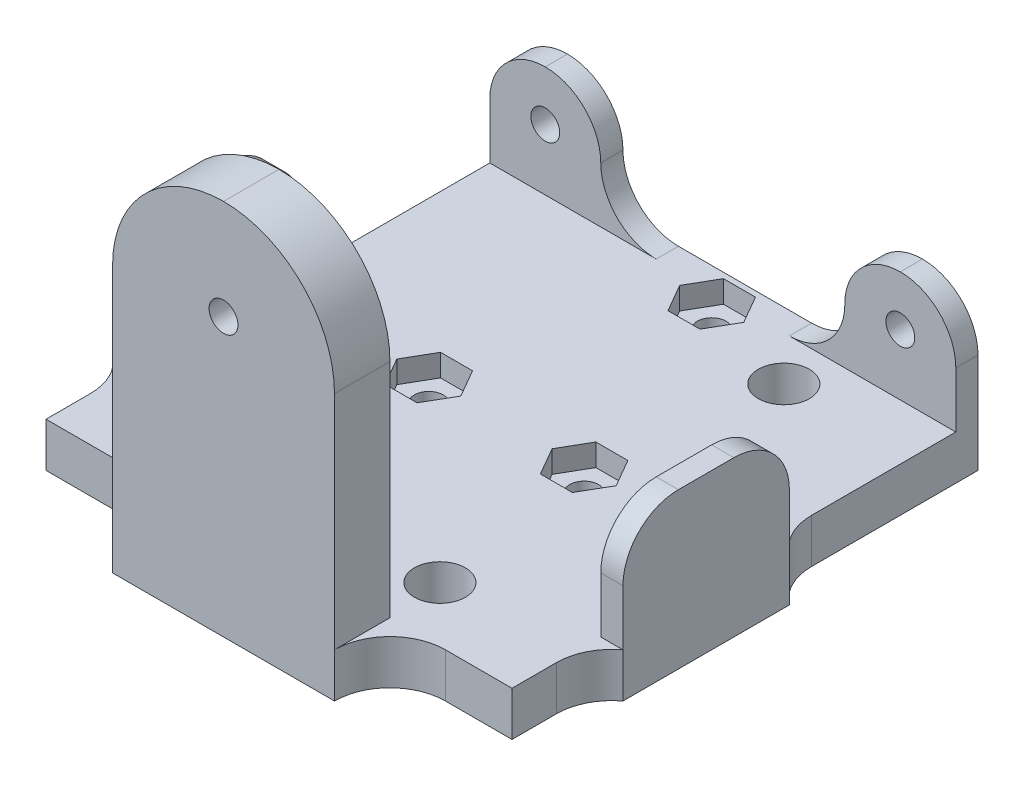
SolidWorks part; units mm, degrees
ref_plane "前视基准面" through (0, 0, 0) normal (0, 0, 1) x (1, 0, 0)
ref_plane "上视基准面" through (0, 0, 0) normal (0, 1, 0) x (1, 0, 0)
ref_plane "右视基准面" through (0, 0, 0) normal (1, 0, 0) x (0, 0, -1)
sketch "草图1" plane through (0, 0, 0) normal (0, 1, 0) x (1, 0, 0)
  line L0 (-23, -10.5) -> (23, -10.5) construction
  line L1 (-23, -23.5) -> (23, -23.5) construction
  line L2 (-23, -23.5) -> (-23, 23.5) construction
  line L3 (-23, 23.5) -> (23, 23.5) construction
  line L4 (23, -23.5) -> (23, 23.5) construction
  line L5 (-23, -23.5) -> (23, 23.5) construction
  line L6 (-23, 23.5) -> (23, -23.5) construction
  line L7 (-23, 4.5) -> (23, 4.5) construction
  line L8 (-21, 23.5) -> (-21, -18.5) construction
  line L9 (21, 23.5) -> (21, -23.5) construction
  line L10 (-23, -18.5) -> (23, -18.5) construction
  line L11 (-10, -23.5) -> (10, -23.5) construction
  line L12 (-23, 21.5) -> (23, 21.5) construction
  line L13 (-11, 23.5) -> (-11, -18.5) construction
  line L14 (11, 23.5) -> (11, -18.5) construction
  line L15 (-21, 23.5) -> (-21, 4.5)
  line L16 (-23, 4.5) -> (-21, 4.5)
  line L17 (-23, -10.5) -> (-21, -10.5)
  line L18 (-21, -10.5) -> (-21, -18.5)
  line L19 (-21, -18.5) -> (-11, -18.5)
  line L20 (-21, -21.4565) -> (-21, -22.1289) construction
  line L21 (-10, -23.5) -> (10, -23.5)
  line L22 (11, -18.5) -> (21, -18.5)
  line L23 (21, -18.5) -> (21, -10.5)
  line L24 (21, -10.5) -> (23, -10.5)
  line L25 (23, 4.5) -> (21, 4.5)
  line L26 (21, 4.5) -> (21, 23.5)
  line L27 (-10, -23.5) -> (-10, -18.5)
  line L28 (-10, -18.5) -> (-11, -18.5)
  line L29 (10, -23.5) -> (10, -18.5)
  line L30 (10, -18.5) -> (11, -18.5)
  line L31 (-23, 4.5) -> (-23, -10.5)
  line L32 (23, 4.5) -> (23, -10.5)
  line L33 (21, 23.5) -> (-21, 23.5)
  point P0 (0, 0)
  point P19 (0, -23.5)
  point P25 (-21, 4.5)
  point P26 (-21, -10.5)
  point P27 (-21, -18.5)
  point P28 (-11, -18.5)
  point P29 (11, -18.5)
  point P30 (21, -18.5)
  point P31 (21, -10.5)
  point P32 (21, 4.5)
  dimension "D1" = 46
  dimension "D2" = 47
  dimension "D3" = 13
  dimension "D4" = 15
  dimension "D5" = 2
  dimension "D6" = 2
  dimension "D7" = 5
  dimension "D8" = 10
  dimension "D9" = 2
  dimension "D10" = 10
  dimension "D11" = 10
extrude "凸台-拉伸1" add sketch "草图1" along normal blind 4
sketch "草图2" plane through (0, 4, 0) normal (0, 1, 0) x (1, 0, 0)
  line L1 (-23, 4.5) -> (-21, 4.5)
  line L2 (-23, 4.5) -> (-23, -10.5)
  line L3 (-23, -10.5) -> (-21, -10.5)
  line L4 (-21, 4.5) -> (-21, -10.5)
  line L5 (21, 4.5) -> (23, 4.5)
  line L6 (21, 4.5) -> (21, -10.5)
  line L7 (21, -10.5) -> (23, -10.5)
  line L8 (23, 4.5) -> (23, -10.5)
  line L9 (-21, 23.5) -> (-11, 23.5)
  line L10 (-21, 23.5) -> (-21, 21.5)
  line L11 (-21, 21.5) -> (-11, 21.5)
  line L12 (-11, 23.5) -> (-11, 21.5)
  line L13 (21, 23.5) -> (11, 23.5)
  line L14 (21, 23.5) -> (21, 21.5)
  line L15 (21, 21.5) -> (11, 21.5)
  line L16 (11, 23.5) -> (11, 21.5)
  line L17 (-10, -18.5) -> (10, -18.5)
  line L18 (-10, -18.5) -> (-10, -23.5)
  line L19 (-10, -23.5) -> (10, -23.5)
  line L20 (10, -18.5) -> (10, -23.5)
  line M5 (-23, 4.5) -> (-23, -10.5)
  line M6 (-23, -10.5) -> (-21, -10.5)
  line M14 (21, -10.5) -> (23, -10.5)
  line M15 (23, -10.5) -> (23, 4.5)
  line M16 (23, 4.5) -> (21, 4.5)
  line M17 (21, 4.5) -> (21, 23.5)
  line M18 (21, 23.5) -> (-21, 23.5)
  line M19 (-21, 23.5) -> (-21, 4.5)
  line M20 (-21, 4.5) -> (-23, 4.5)
  dimension "D1" = 10
  dimension "D2" = 2
  dimension "D3" = 10
  dimension "D4" = 2
extrude "凸台-拉伸2" add sketch "草图2" along normal blind 10 contours L4 M20 M5 M6 | L12 L11 M18 M19 | L16 L15 M18 M17 | L6 M16 M14 M15 region at (22, 4, 3) region at (16, 4, -22.5) region at (-16, 4, -22.5) region at (-22, 4, 3)
sketch "草图3" plane through (0, 4, 0) normal (0, 1, 0) x (1, 0, 0)
  line L1 (-10, -18.5) -> (10, -18.5)
  line L2 (-10, -18.5) -> (-10, -23.5)
  line L3 (-10, -23.5) -> (10, -23.5)
  line L4 (10, -18.5) -> (10, -23.5)
extrude "凸台-拉伸3" add sketch "草图3" along normal blind 30
sketch "草图4" plane through (0, 0, -23.5) normal (0, 0, -1) x (-1, 0, 0)
  line L0 (-11, 9.5) -> (-21, 9.5) construction
  line L1 (-11, 14) -> (-11, 4) construction
  line L2 (-21, 14) -> (-21, 0) construction
  line L3 (11, 9.5) -> (21, 9.5) construction
  line L4 (11, 14) -> (11, 4) construction
  line L6 (21, 14) -> (21, 0) construction
  line L7 (-16, 14) -> (-16, 0) construction
  line L8 (-21, 14) -> (-11, 14) construction
  line L9 (-21, 0) -> (21, 0) construction
  line L10 (16, 14) -> (16, 0) construction
  line L11 (11, 14) -> (21, 14) construction
  circle A0 centre (-16, 9.5) radius 1.3
  circle A1 centre (16, 9.5) radius 1.3
  point P23 (-16, 9.5)
  point P24 (16, 9.5)
  dimension "D1" = 9.5
extrude "切除-拉伸1" cut sketch "草图4" against normal blind 2
sketch "草图5" plane through (0, 0, 18.5) normal (0, 0, -1) x (-1, 0, 0)
  line L0 (-10, 25) -> (10, 25) construction
  line L1 (-10, 34) -> (-10, 4) construction
  line L2 (10, 34) -> (10, 4) construction
  line L3 (0, 34) -> (0, 4) construction
  line L4 (-10, 34) -> (10, 34) construction
  line L5 (-11, 4) -> (11, 4) construction
  circle A0 centre (0, 25) radius 1.3
  point P12 (0, 25)
  dimension "D1" = 21
extrude "切除-拉伸2" cut sketch "草图5" against normal through all
sketch "草图6" plane through (0, 0, 18.5) normal (0, 0, -1) x (-1, 0, 0)
  line L0 (0, 34) -> (0, 4) construction
  line L1 (-10, 34) -> (10, 34) construction
  line L2 (-11, 4) -> (11, 4) construction
  line L3 (10, 25) -> (-10, 25) construction
  line L4 (10, 34) -> (10, 4) construction
  line L5 (-10, 34) -> (-10, 4) construction
  line L7 (2.8868, 25) -> (1.4434, 27.5)
  line L8 (1.4434, 27.5) -> (-1.4434, 27.5)
  line L9 (-1.4434, 27.5) -> (-2.8868, 25)
  line L10 (-2.8868, 25) -> (-1.4434, 22.5)
  line L11 (-1.4434, 22.5) -> (1.4434, 22.5)
  line L12 (1.4434, 22.5) -> (2.8868, 25)
  circle A0 centre (0, 25) radius 2.5 construction
  dimension "D1" = 21
extrude "切除-拉伸3" cut sketch "草图6" against normal blind 3
sketch "草图7" plane through (0, 4, 0) normal (0, 1, 0) x (1, 0, 0)
  line L0 (0, 23.5) -> (0, -18.5) construction
  line L1 (11, 23.5) -> (-11, 23.5) construction
  line L2 (10, -18.5) -> (-10, -18.5) construction
  line L3 (-7, 2) -> (7, 2) construction
  line L4 (0, 2) -> (-18.5, 2) construction
  line L5 (7, 2) -> (9.5, 2) construction
  line L6 (9.5, -13.5) -> (9.5, 17.5) construction
  circle A0 centre (0, 20.5) radius 1.3
  circle A1 centre (-7, 2) radius 1.3
  circle A2 centre (7, 2) radius 1.3
  circle A3 centre (0, -16.5) radius 1.3
  circle A4 centre (-18.5, 2) radius 2.3
  circle A5 centre (9.5, 17.5) radius 2.3
  circle A6 centre (9.5, -13.5) radius 2.3
  point P6 (0, 20.5)
  point P7 (0, 2)
  point P8 (0, -16.5)
  point P11 (0, 2)
  point P25 (9.5, 2)
  dimension "D5" = 18.5
  dimension "D6" = 2.5
  dimension "D1" = 3
  dimension "D2" = 18.5
  dimension "D3" = 7
  dimension "D4" = 18.5
  dimension "D7" = 31
extrude "切除-拉伸5" cut sketch "草图7" against normal through all
sketch "草图8" plane through (0, 4, 0) normal (0, 1, 0) x (1, 0, 0)
  line L0 (0, 23.5) -> (0, -18.5) construction
  line L1 (11, 23.5) -> (-11, 23.5) construction
  line L2 (10, -18.5) -> (-10, -18.5) construction
  line L4 (9.8868, 2) -> (8.4434, 4.5)
  line L5 (8.4434, 4.5) -> (5.5566, 4.5)
  line L6 (5.5566, 4.5) -> (4.1132, 2)
  line L7 (4.1132, 2) -> (5.5566, -0.5)
  line L8 (5.5566, -0.5) -> (8.4434, -0.5)
  line L9 (8.4434, -0.5) -> (9.8868, 2)
  line L10 (-4.1132, 2) -> (-5.5566, 4.5)
  line L11 (-5.5566, 4.5) -> (-8.4434, 4.5)
  line L12 (-8.4434, 4.5) -> (-9.8868, 2)
  line L13 (-9.8868, 2) -> (-8.4434, -0.5)
  line L14 (-8.4434, -0.5) -> (-5.5566, -0.5)
  line L15 (-5.5566, -0.5) -> (-4.1132, 2)
  line L16 (2.8868, 20.5) -> (1.4434, 23)
  line L17 (1.4434, 23) -> (-1.4434, 23)
  line L18 (-1.4434, 23) -> (-2.8868, 20.5)
  line L19 (-2.8868, 20.5) -> (-1.4434, 18)
  line L20 (-1.4434, 18) -> (1.4434, 18)
  line L21 (1.4434, 18) -> (2.8868, 20.5)
  line L22 (2.8868, -16.5) -> (1.4434, -14)
  line L23 (1.4434, -14) -> (-1.4434, -14)
  line L24 (-1.4434, -14) -> (-2.8868, -16.5)
  line L25 (-2.8868, -16.5) -> (-1.4434, -19)
  line L26 (-1.4434, -19) -> (1.4434, -19)
  line L27 (1.4434, -19) -> (2.8868, -16.5)
  circle A0 centre (7, 2) radius 2.5 construction
  circle A1 centre (-7, 2) radius 2.5 construction
  circle A2 centre (0, 20.5) radius 2.5 construction
  circle A3 centre (0, -16.5) radius 2.5 construction
  point P6 (0, 20.5)
  point P7 (7, 2)
  point P9 (-7, 2)
  point P11 (0, -16.5)
extrude "切除-拉伸6" cut sketch "草图8" against normal blind 2 and the other way blind 2
fillet "圆角1" radius 10 2 edges at (-10, 34, 21) (10, 34, 21)
fillet "圆角2" radius 5 14 edges at (21, 2, 10.5) (21, 2, -4.5) (22, 14, 10.5) (22, 14, -4.5) (-21, 2, 10.5) (-21, 2, -4.5) (-22, 14, 10.5) (-22, 14, -4.5) (11, 4, -22.5) (-11, 4, -22.5) (-21, 14, -22.5) (-11, 14, -22.5) (11, 14, -22.5) (21, 14, -22.5)
fillet "圆角3" radius 5 2 edges at (10, 2, 18.5) (-10, 2, 18.5)
